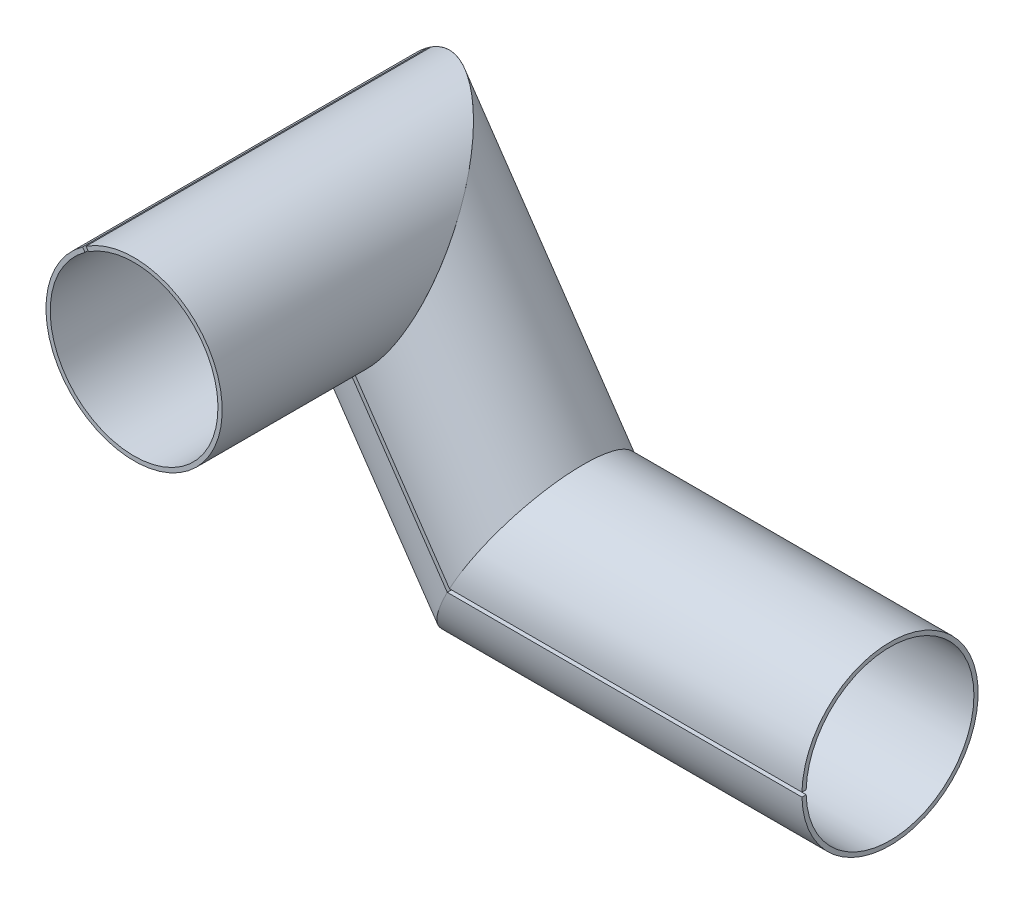
SolidWorks part; units mm, degrees
ref_plane "前视基准面" through (0, 0, 0) normal (0, 0, 1) x (1, 0, 0)
ref_plane "上视基准面" through (0, 0, 0) normal (0, 1, 0) x (1, 0, 0)
ref_plane "右视基准面" through (0, 0, 0) normal (1, 0, 0) x (0, 0, -1)
sketch "草图1" plane through (0, 0, 0) normal (0, 0, 1) x (1, 0, 0)
  line L0 (-34.258, 50.0532) -> (0, 0) construction
  line L1 (0, 0) -> (83.3861, 0) construction
  line L2 (83.3861, 20.786) -> (83.3861, -20.786) construction
  line L3 (-34.258, 50.0532) -> (-13.472, 50.0532) construction
  line L4 (-34.258, 29.2671) -> (-34.258, 70.8392) construction
  line L5 (83.3861, -20.786) -> (-10.9618, -20.786) construction
  line L6 (-10.9618, -20.786) -> (-51.4111, 38.313) construction
  line L7 (83.3861, 20.786) -> (10.9618, 20.786) construction
  line L8 (10.9618, 20.786) -> (-17.105, 61.7933) construction
  line L9 (-10.9618, -20.786) -> (10.9618, 20.786) construction
  line L10 (83.3861, 0) -> (84.3861, 0) construction
  line L11 (-34.258, 50.0532) -> (0, 0)
  line L12 (0, 0) -> (83.3861, 0)
  line L13 (-17.105, 61.7933) -> (-34.258, 86.855) construction
  line L14 (-34.258, 50.0532) -> (-51.4111, 75.1149)
  line L15 (-51.4111, 75.1149) -> (-34.258, 86.855) construction
  line L16 (0, 0) -> (0, -60.6542) construction
  circle A0 centre (-34.258, 50.0532) radius 20.786 construction
  dimension "D1" = 60.6542
  dimension "R" = 20.786
  dimension "L1" = 117.6441
  dimension "B" = 55.611
  dimension "L2" = 70.8392
  dimension "t" = 1
  dimension "L3" = 60.6542
sketch "草图2" plane through (0, 0, 0) normal (1, 0, 0) x (0, 0, -1)
  circle A0 centre (0, 0) radius 20.786
extrude "拉伸-薄壁1" add sketch "草图2" along normal up to vertex (83.3861 mm away) and the other way up to vertex (10.9618 mm away) thin up to point (83.3861, -20.786, 0) other way up to point (-10.9618, -20.786, 0) thin type one direction reverse wall 1
ref_plane "基准面1" through (-34.258, 50.0532, 0) normal (0.5648, -0.8252, 0) x (0.8252, 0.5648, 0)
sketch "草图3" plane through (-34.258, 50.0532, 0) normal (0.5648, -0.8252, 0) x (0.8252, 0.5648, 0)
  line L0 (0, 0) -> (0, 60.6542) construction
  line L1 (0, 0) -> (0, -20.786) construction
  circle A0 centre (0, 0) radius 20.786
  dimension "L3" = 60.6542
extrude "拉伸-薄壁2" add sketch "草图3" along normal up to vertex (71.616 mm away) and the other way up to vertex (30.3697 mm away) separate body thin up to point (-10.9618, -20.786, 0) other way up to point (-34.258, 86.855, 0) thin type one direction reverse wall 1
sketch "草图4" plane through (0, 0, 0) normal (0, 0, 1) x (1, 0, 0)
  circle A0 centre (-34.258, 50.0532) radius 20.786
extrude "拉伸-薄壁3" add sketch "草图4" along normal up to vertex (60.6542 mm away) and the other way up to vertex (20.786 mm away) separate body thin up to point (-34.258, 50.0532, 60.6542) other way up to point (-34.258, 50.0532, -20.786) thin type one direction reverse wall 1
sketch "草图5" plane through (0, 0, 0) normal (0, 0, 1) x (1, 0, 0)
  line L0 (-10.9618, -20.786) -> (10.9618, 20.786) construction
  line L1 (-10.9618, -20.786) -> (10.9618, 20.786)
extrude "切除-拉伸2" cut sketch "草图5" against normal through all and the other way through all
extrude "切除-拉伸3" cut sketch "草图5<2>" against normal through all and the other way through all flip side to cut
sketch "草图5<2>" plane through (0, 0, 0) normal (0, 0, 1) x (1, 0, 0) same geometry as "草图5"
ref_plane "基准面2" through (0, 0, 0) normal (0.8252, 0.5648, 0) x (0, 0, -1)
sketch "草图6" plane through (0, 0, 0) normal (0.8252, 0.5648, 0) x (0, 0, -1)
  line L0 (-60.6542, 0) -> (60.6542, 121.3084)
  line L1 (0, 0) -> (-60.6542, 0) construction
  dimension "D1" = 45
extrude "切除-拉伸4" cut sketch "草图6" against normal through all and the other way through all
extrude "切除-拉伸5" cut sketch "草图6<2>" against normal through all and the other way through all flip side to cut
sketch "草图6<2>" plane through (0, 0, 0) normal (0.8252, 0.5648, 0) x (0, 0, -1) same geometry as "草图6"
extrude "切除-拉伸-薄壁1" cut sketch "草图1" along normal through all thin thin type mid plane wall 1
sketch "草图7" plane through (-34.258, 50.0532, 0) normal (0.5648, -0.8252, 0) x (0.8252, 0.5648, 0)
  line L0 (0, 0) -> (0, 60.6542) construction
  line L1 (0, 0) -> (0, 60.6542)
  line L2 (0, 0) -> (0, -20.786)
extrude "切除-拉伸-薄壁2" cut sketch "草图7" against normal through all thin thin type mid plane wall 1
equation "\"D5@拉伸-薄壁1\" = \"t@草图1\""
equation "\"D5@拉伸-薄壁2\" =  \"t@草图1\""
equation "\"D5@拉伸-薄壁3\" =  \"t@草图1\""
equation "\"L3@草图3\" = \"L3@草图1\""
